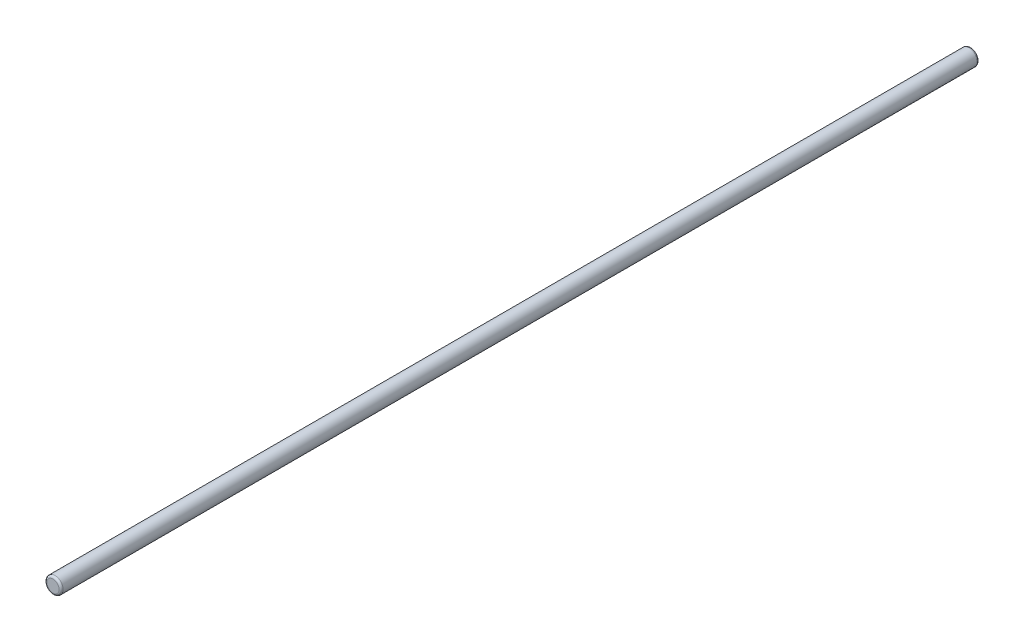
SolidWorks part; units mm, degrees
ref_plane "Front Plane" through (0, 0, 0) normal (0, 0, 1) x (1, 0, 0)
ref_plane "Top Plane" through (0, 0, 0) normal (0, 1, 0) x (1, 0, 0)
ref_plane "Right Plane" through (0, 0, 0) normal (1, 0, 0) x (0, 0, -1)
sketch "Sketch1" plane through (0, 0, 0) normal (0, 0, 1) x (1, 0, 0)
  circle A0 centre (0, 0) radius 4
extrude "Extrude2" add sketch "Sketch1" along normal blind 225 and the other way blind 225
fillet "Fillet2" radius 1 1 edges at (4, 0, -225)
fillet "Fillet3" radius 1 1 edges at (4, 0, 225)
